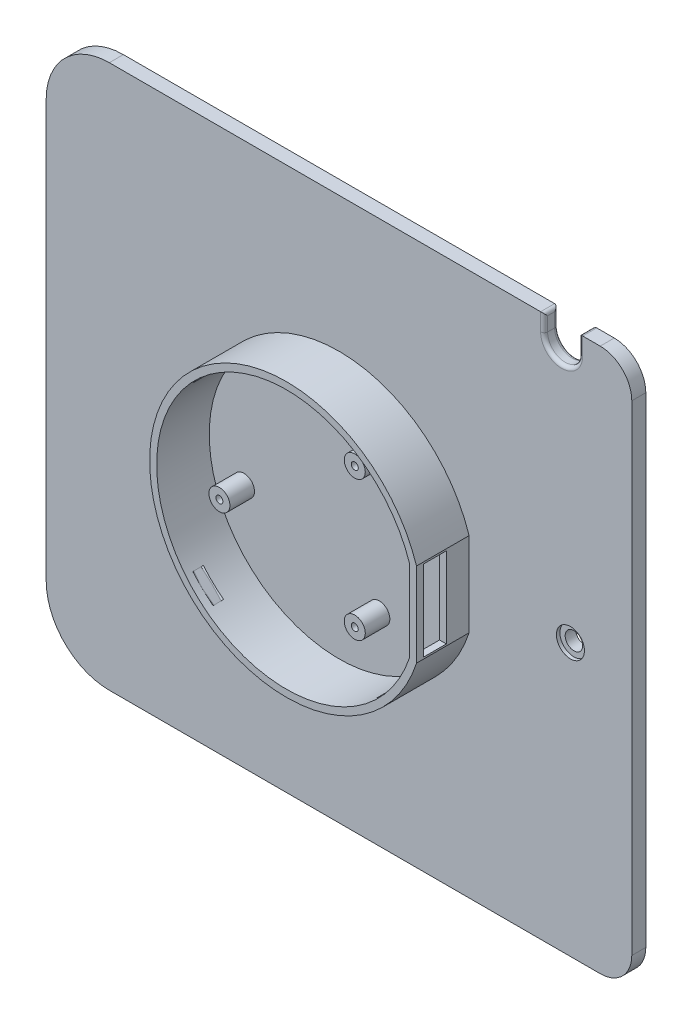
SolidWorks part; units mm, degrees
ref_plane "Front" through (0, 0, 0) normal (0, 0, 1) x (1, 0, 0)
ref_plane "Top" through (0, 0, 0) normal (0, 1, 0) x (1, 0, 0)
ref_plane "Right" through (0, 0, 0) normal (1, 0, 0) x (0, 0, -1)
sketch "ｽｹｯﾁ1" plane through (0, 0, 0) normal (0, 0, 1) x (1, 0, 0)
  line L1 (-83.5, 77.5) -> (83.5, 77.5)
  line L2 (-83.5, 77.5) -> (-83.5, -77.5)
  line L3 (-83.5, -77.5) -> (83.5, -77.5)
  line L4 (83.5, 77.5) -> (83.5, -77.5)
  line L5 (-83.5, 77.5) -> (83.5, -77.5) construction
  line L6 (-83.5, -77.5) -> (83.5, 77.5) construction
  point P0 (0, 0)
  dimension "D1" = 155
  dimension "D2" = 167
extrude "ﾎﾞｽ - 押し出し1" add sketch "ｽｹｯﾁ1" along normal blind 4
fillet "ﾌｨﾚｯﾄ1" radius 9 2 edges at (83.5, -77.5, 2) (83.5, 77.5, 2)
fillet "ﾌｨﾚｯﾄ2" radius 18 2 edges at (-83.5, -77.5, 2) (-83.5, 77.5, 2)
sketch "ｽｹｯﾁ2" plane through (0, 0, 4) normal (0, 0, 1) x (1, 0, 0)
  line L0 (74.5, 77.5) -> (-65.5, 77.5) construction
  line L1 (58.5, 77.5) -> (68.5, 77.5)
  line L2 (58.5, 77.5) -> (58.5, 72.5)
  line L4 (68.5, 77.5) -> (68.5, 72.5)
  line L5 (63.5, 77.5) -> (63.5, 62.7788) construction
  line L6 (83.5, -68.5) -> (83.5, 68.5) construction
  arc A0 (58.5, 72.5) -> (68.5, 72.5) centre (63.5, 72.5) ccw
  dimension "D4" = 5
  dimension "D1" = 20
  dimension "D2" = 10
  dimension "D3" = 5
extrude "ｶｯﾄ - 押し出し1" cut sketch "ｽｹｯﾁ2" against normal up to next
hole_wizard "穴1" positions "ｽｹｯﾁ9" profile "ｽｹｯﾁ10" legacy end condition up to next
sketch "ｽｹｯﾁ9" plane through (0, 0, 4) normal (0, 0, 1) x (1, 0, 0)
  line L0 (58.5, 77.5) -> (-65.5, 77.5) construction
  line L2 (83.5, -68.5) -> (83.5, 68.5) construction
  line L3 (-65.5, -77.5) -> (74.5, -77.5) construction
  point P0 (66, 0)
  dimension "D1" = 77.5
  dimension "D2" = 17.5
  dimension "D3" = 77.5
sketch "ｽｹｯﾁ10" plane through (66, 0, 4) normal (1, 0, 0) x (0, -1, 0)
  line L0 (0, 0) -> (0, 4)
  line L1 (0, 4) -> (2.5, 4)
  line L2 (2.5, 4) -> (2.5, 1)
  line L3 (2.5, 1) -> (4, 1)
  line L4 (4, 1) -> (4, 0)
  line L5 (4, 0) -> (0, 0)
  line L6 (0, 110) -> (0, -10) construction
  dimension "直径" = 5
  dimension "深さ" = 4
  dimension "座ぐり穴-直径" = 8
  dimension "座ぐり穴-深さ" = 1
sketch "ｽｹｯﾁ11" plane through (0, 0, 4) normal (0, 0, 1) x (1, 0, 0)
  line L0 (91.8904, 0) -> (-117.2241, 0) construction
  line L1 (35.1675, 11.5) -> (35.1675, -11.5)
  line L2 (37.108, 12) -> (37.108, -12)
  arc A2 (35.1675, -11.5) -> (35.1675, 11.5) centre (0, 0) cw
  arc A3 (37.108, 12) -> (37.108, -12) centre (0, 0) ccw
  dimension "D1" = 23
  dimension "D2" = 37
  dimension "D4" = 24
  dimension "D3" = 39
  dimension "D5" = 1.9405
extrude "ﾎﾞｽ - 押し出し3" add sketch "ｽｹｯﾁ11" along normal blind 15
sketch "ｽｹｯﾁ13" plane through (37.108, 0, 0) normal (1, 0, 0) x (0, 0, -1)
  line L0 (11.4447, 0) -> (-37.1117, 0) construction
  line L1 (-17, 11.5) -> (-10.5, 11.5)
  line L2 (-17, 11.5) -> (-17, -11.5)
  line L3 (-17, -11.5) -> (-10.5, -11.5)
  line L4 (-10.5, 11.5) -> (-10.5, -11.5)
  line L5 (-4, -12) -> (-4, 12) construction
  dimension "D1" = 6.5
  dimension "D2" = 6.5
  dimension "D3" = 23
extrude "ｶｯﾄ - 押し出し2" cut sketch "ｽｹｯﾁ13" against normal up to next
sketch "ｽｹｯﾁ14" plane through (0, 0, 0) normal (0, 1, 0) x (1, 0, 0)
  line L0 (0, 0) -> (5.3431, -124.3448) construction
ref_plane "平面1" through (0, 0, 0) normal (-0.7065, 0.7071, 0.0304) x (0.7076, 0.7065, 0.0126)
ref_plane "平面2" through (-24.7259, 24.7487, 1.0625) normal (-0.7065, 0.7071, 0.0304) x (0.7076, 0.7065, 0.0126)
sketch "ｽｹｯﾁ15" plane through (-24.7259, 24.7487, 1.0625) normal (-0.7065, 0.7071, 0.0304) x (0.7076, 0.7065, 0.0126)
  line L0 (0, -53.3214) -> (0, 75.9558) construction
  line L1 (12.9242, -17.7742) -> (-21.95, -17.7742) construction
  line L2 (-4, -15.7742) -> (4, -15.7742)
  line L3 (-4, -15.7742) -> (-4, -12.7742)
  line L4 (-4, -12.7742) -> (4, -12.7742)
  line L5 (4, -15.7742) -> (4, -12.7742)
  ellipse E1 centre (0.2387, -18.9897) end of major axis (-36.7584, -19.4548) minor radius 1.1232 (33.249, -19.0824) -> (17.0006, -19.7806) ccw construction
  dimension "D1" = 3
  dimension "D2" = 2
  dimension "D3" = 8
extrude "ｶｯﾄ - 押し出し3" cut sketch "ｽｹｯﾁ15" along normal blind 2.5
fillet "ﾌｨﾚｯﾄ3" radius 0.5 2 edges at (-26.3316, 26.1287, 13.9056) (-26.2939, 26.0377, 16.904)
pattern_circular "円形ﾊﾟﾀｰﾝ1" count 4 every 90 about axis through (0, 0, 19) along (0, 0, -1) of "ｶｯﾄ - 押し出し3", "ﾌｨﾚｯﾄ3"
sketch "ｽｹｯﾁ19" plane through (0, 0, 0) normal (0, 0, -1) x (-1, 0, 0)
  line L0 (13.003, 0) -> (129.8001, 0) construction
  line L1 (65.5, -77.5) -> (-74.5, -77.5) construction
  line L2 (-58.5, 77.5) -> (65.5, 77.5) construction
  line L3 (83.5, 59.5) -> (83.5, -59.5) construction
  line L4 (77.5, -55) -> (87.5, -55)
  line L5 (77.5, -55) -> (77.5, -35)
  line L6 (77.5, -35) -> (87.5, -35)
  line L7 (87.5, -55) -> (87.5, -35)
  dimension "D1" = 55
  dimension "D2" = 4
  dimension "D3" = 20
  dimension "D4" = 10
extrude "ﾎﾞｽ - 押し出し5" add sketch "ｽｹｯﾁ19" along normal blind 3
fillet "ﾌｨﾚｯﾄ5" radius 1 9 edges at (-82.5, -35, -3) (-87.5, -45, -3) (-82.5, -55, -3) (-77.5, -45, -3) (-87.5, -35, -1.5) (-87.5, -55, -1.5) (-80.5, -35, 0) (-77.5, -45, 0) (-80.5, -55, 0)
ref_plane "平面3" through (37.108, 12, 19) normal (0, 1, 0) x (1, 0, 0)
mirror "ﾐﾗｰ2" about plane through (0, 0, 0) normal (0, 1, 0) of "ﾎﾞｽ - 押し出し5", "ﾌｨﾚｯﾄ5"
fillet "ﾌｨﾚｯﾄ6" radius 1 8 edges at (68.5, 75, 0) (58.5, 75, 0) (58.5, 75, 4) (68.5, 75, 4) (63.5, 67.5, 0) (63.5, 67.5, 4) (68.5, 77.5, 2) (58.5, 77.5, 2)
sketch "ｽｹｯﾁ20" plane through (0, 0, 4) normal (0, 0, 1) x (1, 0, 0)
  line L0 (0, 0) -> (29.5889, 0) construction
  line L1 (50, 0) -> (-50, 0) construction
  line L2 (11.5, 19.8864) -> (11.5, -19.9136) construction
  circle A0 centre (11.5, -19.9136) radius 3
  circle A1 centre (11.5, 19.8864) radius 3
  circle A2 centre (-27.1, -7.7) radius 3
  point P9 (11.5, -0.0136)
  dimension "D4" = 6
  dimension "D1" = 11.5
  dimension "D2" = 19.9
  dimension "D3" = 19.9
  dimension "D5" = 27.1
  dimension "D6" = 7.7
extrude "ﾎﾞｽ - 押し出し6" add sketch "ｽｹｯﾁ20" along normal blind 7
hole_wizard "Ø2.0 (2) 直径の穴1" positions "ｽｹｯﾁ23" profile "ｽｹｯﾁ24" hole size "Ø2.0" standard "ISO"
sketch "ｽｹｯﾁ23" plane through (0, 0, 11) normal (0, 0, 1) x (1, 0, 0)
  circle A0 centre (11.5, -19.9136) radius 3 construction
  circle A1 centre (11.5, 19.8864) radius 3 construction
  circle A2 centre (-27.1, -7.7) radius 3 construction
  point P0 (11.5, 19.8864)
  point P2 (11.5, -19.9136)
  point P11 (-27.1, -7.7)
sketch "ｽｹｯﾁ24" plane through (11.5, 19.8864, 11) normal (1, 0, 0) x (0, -1, 0)
  line L0 (0, 0) -> (0, 5.6009)
  line L1 (0, 5.6009) -> (1, 5)
  line L2 (1, 5) -> (1, 0)
  line L5 (1, 0) -> (0, 0)
  line L10 (0, 5.6009) -> (-1, 5) construction
  line L11 (0, -6.35) -> (0, 107.95) construction
  dimension "穴の直径" = 2
  dimension "穴の深さ" = 5
  dimension "ﾄﾞﾘﾙ角度" = 118
